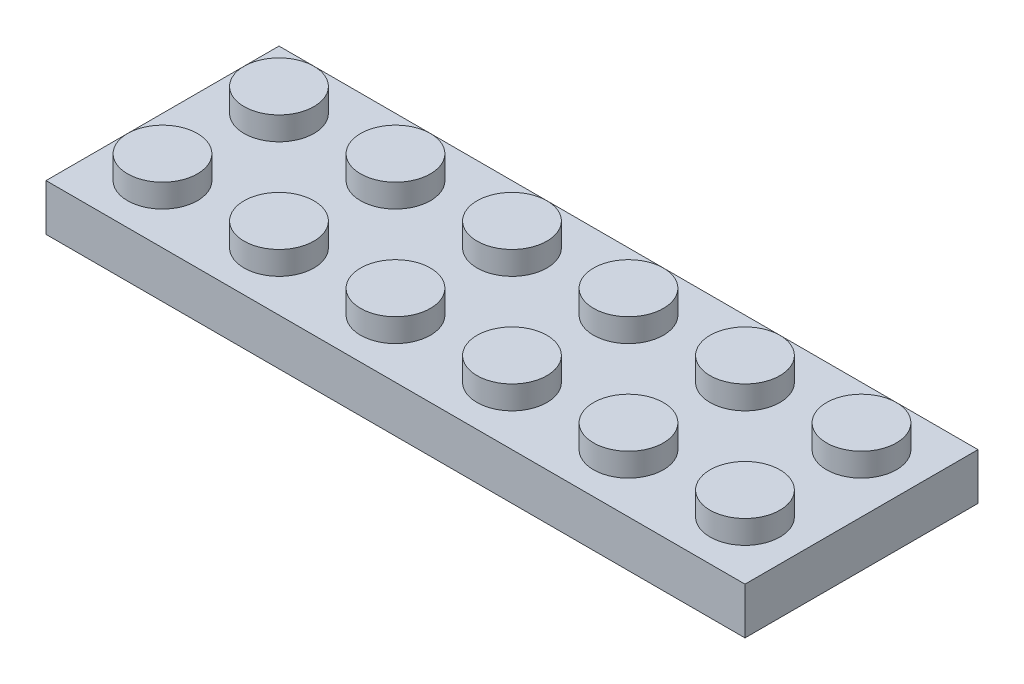
SolidWorks part; units mm, degrees
ref_plane "Front Plane" through (0, 0, 0) normal (0, 0, 1) x (1, 0, 0)
ref_plane "Top Plane" through (0, 0, 0) normal (0, 1, 0) x (1, 0, 0)
ref_plane "Right Plane" through (0, 0, 0) normal (1, 0, 0) x (0, 0, -1)
sketch "Sketch1" plane through (0, 0, 0) normal (0, 1, 0) x (1, 0, 0)
  line L1 (-15, -5) -> (15, -5)
  line L2 (-15, -5) -> (-15, 5)
  line L3 (-15, 5) -> (15, 5)
  line L4 (15, -5) -> (15, 5)
  line L5 (-15, -5) -> (15, 5) construction
  line L6 (-15, 5) -> (15, -5) construction
  line L7 (-14, 4) -> (14, 4)
  line L8 (-14, 4) -> (-14, -4)
  line L9 (-14, -4) -> (14, -4)
  line L10 (14, 4) -> (14, -4)
  line L11 (-14, 4) -> (14, -4) construction
  line L12 (-14, -4) -> (14, 4) construction
  circle A0 centre (-12.5, 2.5) radius 1.5
  circle A1 centre (-7.5, 2.5) radius 1.5
  circle A2 centre (-2.5, 2.5) radius 1.5
  circle A3 centre (2.5, 2.5) radius 1.5
  circle A4 centre (7.5, 2.5) radius 1.5
  circle A5 centre (12.5, 2.5) radius 1.5
  circle A6 centre (-7.5, -2.5) radius 1.5
  circle A7 centre (-2.5, -2.5) radius 1.5
  circle A8 centre (2.5, -2.5) radius 1.5
  circle A9 centre (7.5, -2.5) radius 1.5
  circle A10 centre (12.5, -2.5) radius 1.5
  circle A11 centre (-12.5, -2.5) radius 1.5
  circle A12 centre (-10, 0) radius 2.0355
  circle A13 centre (-5, 0) radius 2.0355
  circle A14 centre (0, 0) radius 2.0355
  circle A15 centre (5, 0) radius 2.0355
  circle A16 centre (10, 0) radius 2.0355
  circle A17 centre (-10, 0) radius 1.5
  circle A18 centre (-5, 0) radius 1.5
  circle A19 centre (0, 0) radius 1.5
  circle A20 centre (5, 0) radius 1.5
  circle A21 centre (10, 0) radius 1.5
  point P0 (0, 0)
  dimension "D5" = 3
  dimension "D11" = 3
  dimension "D1" = 10
  dimension "D2" = 30
  dimension "D3" = 2.5
  dimension "D4" = 2.5
  dimension "D9" = 1
  dimension "D10" = 1
  dimension "D6" = 6
  dimension "D7" = 2
  dimension "D8" = 5
  dimension "D12" = 5
extrude "Boss-Extrude1" add sketch "Sketch1" along normal blind 2 contours A2 | A1 | A0 | A11 | A6 | A7 | A3 | A4 | A5 | A10 | A9 | A8 region at (-12.5, 0, -2.5) region at (-7.5, 0, -2.5) region at (-12.5, 0, 2.5) region at (-2.5, 0, -2.5) region at (2.5, 0, -2.5) region at (-7.5, 0, 2.5) region at (7.5, 0, -2.5) region at (-2.5, 0, 2.5) region at (12.5, 0, -2.5) region at (2.5, 0, 2.5) region at (7.5, 0, 2.5) region at (12.5, 0, 2.5)
extrude "Boss-Extrude2" add sketch "Sketch1<3>" along normal blind 1 contours L2 L3 L4 L1
sketch "Sketch1<3>" plane through (0, 0, 0) normal (0, 1, 0) x (1, 0, 0) same geometry as "Sketch1"
extrude "Boss-Extrude3" add sketch "Sketch1<4>" against normal blind 1 contours L1 L4 L3 L2 L7 L10 L9 L8 | A12 A17 | A13 A18 | A14 A19 | A15 A20 | A16 A21 region at (-14.6838, 0, 0) region at (-10, 0, -1.978) region at (-3.1726, 0, -0.7569) region at (1.8274, 0, -0.7569) region at (6.8274, 0, -0.7569) region at (11.8274, 0, -0.7569)
sketch "Sketch1<4>" plane through (0, 0, 0) normal (0, 1, 0) x (1, 0, 0) same geometry as "Sketch1"
